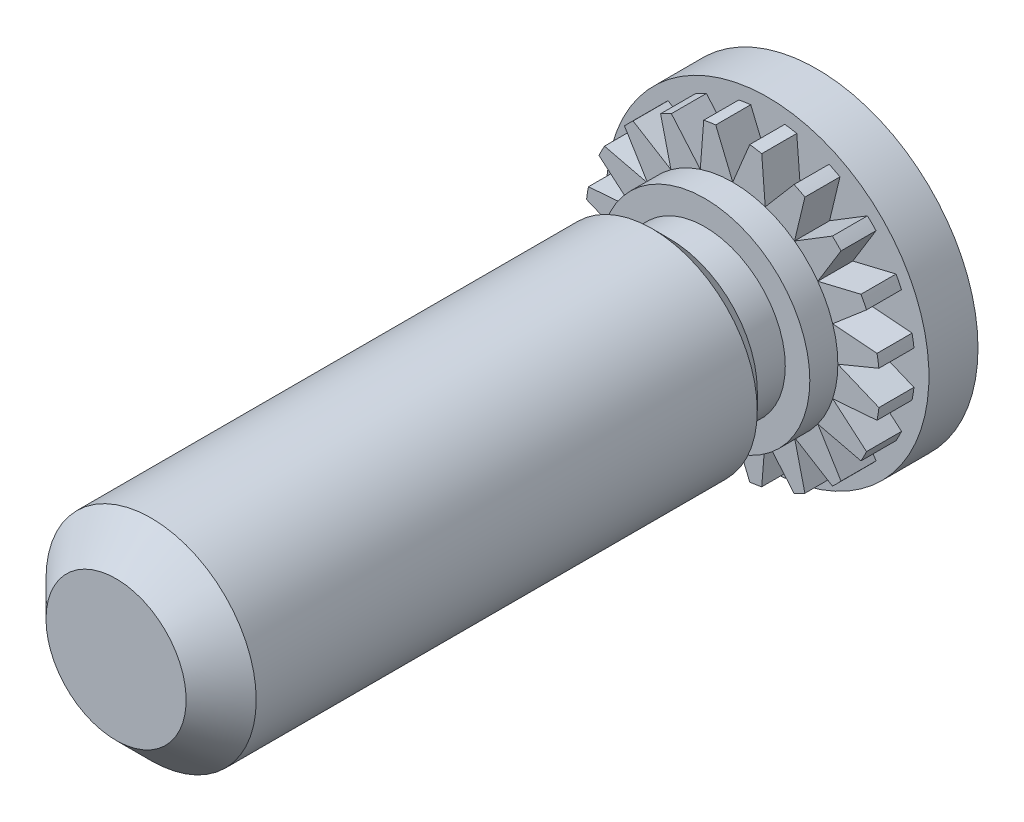
SolidWorks part; units mm, degrees
ref_plane "Спереди" through (0, 0, 0) normal (0, 0, 1) x (1, 0, 0)
ref_plane "Сверху" through (0, 0, 0) normal (0, 1, 0) x (1, 0, 0)
ref_plane "Справа" through (0, 0, 0) normal (1, 0, 0) x (0, 0, -1)
sketch "Эскиз1" plane through (0, 0, 0) normal (0, 0, 1) x (1, 0, 0)
  circle A0 centre (0, 0) radius 2.3
  dimension "D1" = 4.6
extrude "Вытянуть1" add sketch "Эскиз1" along normal blind 1.2
ref_axis "Ось1" through (0, 0, 10.6426) along (0, 0, -1)
sketch "Эскиз2" plane through (0, 0, 1.2) normal (0, 0, 1) x (1, 0, 0)
  circle A0 centre (0, 0) radius 1.5
  dimension "D1" = 3
extrude "Вытянуть2" add sketch "Эскиз2" along normal blind 1.5
sketch "Эскиз3" plane through (0, 0, 1.2) normal (0, 0, 1) x (1, 0, 0)
  line L0 (0, 0) -> (0, 2.3) construction
  line L1 (-0.3314, 2.3) -> (0.3314, 2.3)
  line L2 (0.3314, 2.3) -> (0, 1.5)
  line L3 (0, 1.5) -> (-0.3314, 2.3)
  circle A0 centre (0, 0) radius 2.3 construction
  circle A1 centre (0, 0) radius 1.5 construction
  dimension "D1" = 45
extrude "Вырез-Вытянуть1" cut sketch "Эскиз3" against normal blind 0.5
pattern_circular "Круговой массив1" count 20 over 360 about axis through (0, 0, 10.6426) along (0, 0, -1) of "Вырез-Вытянуть1"
sketch "Эскиз4" plane through (0, 0, 0) normal (0, 1, 0) x (1, 0, 0)
  line L0 (0, -1.85) -> (1.5, -1.85) construction
  line L1 (0, -4.6295) -> (0, 2.1879) construction
  line L2 (-1.5, -2.7) -> (1.5, -2.7) construction
  line L3 (1.5, -1.6) -> (1.15, -1.6)
  line L4 (1.5, -1.6) -> (1.5, -2.1)
  line L5 (1.5, -2.1) -> (1.15, -2.1)
  line L6 (1.15, -1.6) -> (1.15, -2.1)
  dimension "D1" = 0.5
  dimension "D2" = 0.6
  dimension "D3" = 1.5
  dimension "D4" = 0.35
revolve "Вырез-Повернуть1" cut sketch "Эскиз4" angle 360 about axis through (0, 0, 10.6426) along (0, 0, -1)
sketch "Эскиз6" plane through (0, 0, 0) normal (1, 0, 0) x (0, 0, -1)
  line L0 (-2.7, 0) -> (-10, 0)
  line L1 (-2.7, 1.5) -> (-2.7, -1.5) construction
  line L2 (-4.6295, 0) -> (2.1879, 0) construction
  line L3 (-10, 0) -> (-10, -1.5)
  line L4 (-10, -1.5) -> (-2.7, -1.5)
  line L5 (-2.7, -1.5) -> (-2.7, 0)
  line L6 (0, -2.3) -> (0, 2.3) construction
  dimension "D1" = 10
  dimension "D2" = 1.5
revolve "Повернуть1" add sketch "Эскиз6" angle 360 about L0
chamfer "Фаска2" distance 0.5 angle 45 1 edges at (-1.5, 0, 10)
sketch "Эскиз7" plane through (0, 0, 1.2) normal (0, 0, 1) x (1, 0, 0)
  circle A0 centre (0, 0) radius 2.1
  circle A1 centre (0, 0) radius 2.3
  arc A2 (-1.0781, 2.0317) -> (-1.5991, 1.6532) centre (0, 0) ccw construction
  dimension "D1" = 0.2
extrude "Вырез-Вытянуть2" cut sketch "Эскиз7" against normal up to surface (0.5 mm away) up to face at (-1.9266, 0.626, 0.7)
chamfer "Фаска3" distance 0.25 angle 45 1 edges at (1.5, 0, 2.1)
